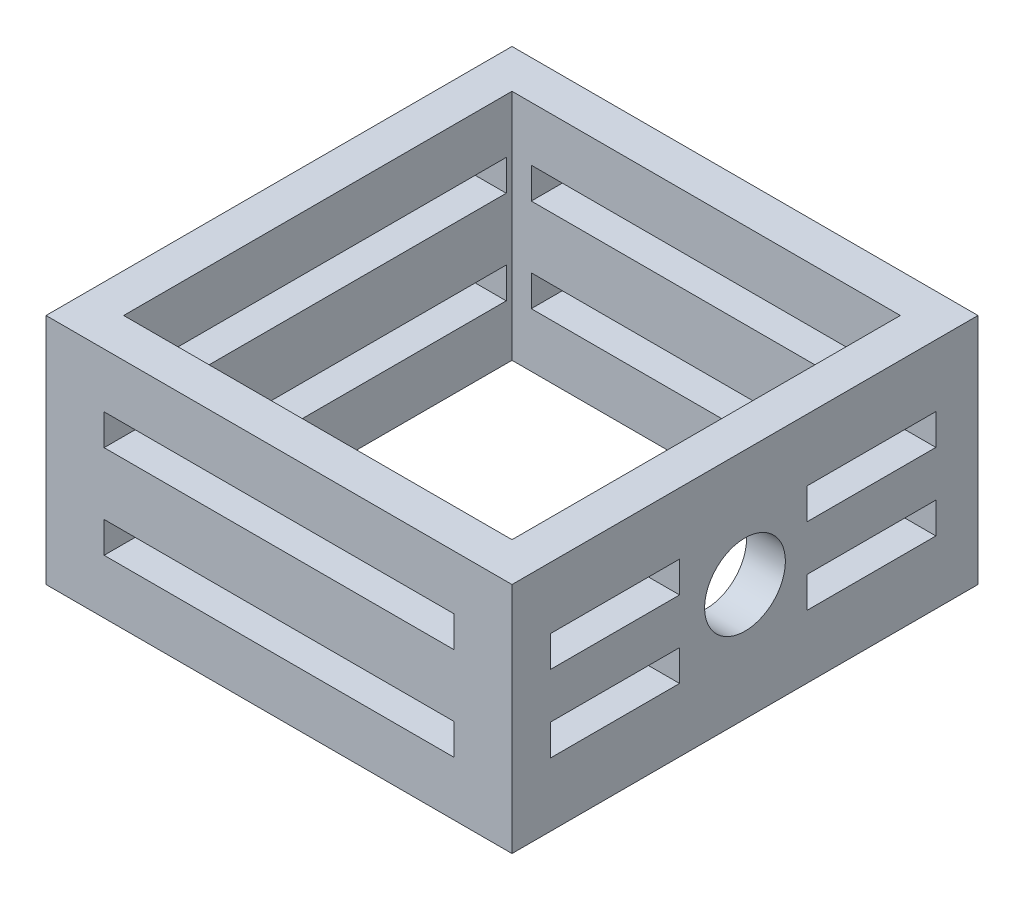
SolidWorks part; units mm, degrees
ref_plane "Front Plane" through (0, 0, 0) normal (0, 0, 1) x (1, 0, 0)
ref_plane "Top Plane" through (0, 0, 0) normal (0, 1, 0) x (1, 0, 0)
ref_plane "Right Plane" through (0, 0, 0) normal (1, 0, 0) x (0, 0, -1)
sketch "Sketch2" plane through (0, 0, 0) normal (0, 1, 0) x (1, 0, 0)
  line L1 (-15, 15) -> (15, 15)
  line L2 (-15, 15) -> (-15, -15)
  line L3 (-15, -15) -> (15, -15)
  line L4 (15, 15) -> (15, -15)
  line L5 (-15, 15) -> (15, -15) construction
  line L6 (-15, -15) -> (15, 15) construction
  point P0 (0, 0)
  dimension "D1" = 30
  dimension "D2" = 30
extrude "Boss-Extrude1" add sketch "Sketch2" along normal blind 10 contours L2 L1 L4 L3
sketch "Sketch3" plane through (0, 10, 0) normal (0, 1, 0) x (1, 0, 0)
  line L1 (-15, 15) -> (15, 15)
  line L2 (-15, 15) -> (-15, -15)
  line L3 (-15, -15) -> (15, -15)
  line L4 (15, 15) -> (15, -15)
  line L5 (-15, 15) -> (15, -15) construction
  line L6 (-15, -15) -> (15, 15) construction
  line L7 (-12.5, 12.5) -> (12.5, 12.5)
  line L8 (-12.5, 12.5) -> (-12.5, -12.5)
  line L9 (-12.5, -12.5) -> (12.5, -12.5)
  line L10 (12.5, 12.5) -> (12.5, -12.5)
  line L11 (-12.5, 12.5) -> (12.5, -12.5) construction
  line L12 (-12.5, -12.5) -> (12.5, 12.5) construction
  point P0 (0, 0)
  point P7 (0, 0)
  dimension "D1" = 25
extrude "Boss-Extrude2" add sketch "Sketch3" along normal blind 15 separate body
sketch "Sketch4" plane through (0, 25, 0) normal (0, 1, 0) x (1, 0, 0)
  line L1 (-15, 15) -> (15, 15)
  line L2 (-15, 15) -> (-15, -15)
  line L3 (-15, -15) -> (15, -15)
  line L4 (15, 15) -> (15, -15)
  line L5 (-15, 15) -> (15, -15) construction
  line L6 (-15, -15) -> (15, 15) construction
  point P0 (0, 0)
extrude "Boss-Extrude3" add sketch "Sketch4" along normal blind 15 separate body
sketch "Sketch5" plane through (0, 40, 0) normal (0, 1, 0) x (1, 0, 0)
  circle A0 centre (0, 0) radius 3.05
extrude "Cut-Extrude1" cut sketch "Sketch5" against normal up to surface (40 mm away) up to face at (0, 0, 0)
delete or keep bodies "Body-Delete/Keep 2" type delete bodies bodies 104 105
sketch "Sketch6" plane through (15, 0, 0) normal (1, 0, 0) x (0, 0, -1)
  line L0 (-15, 17.5) -> (15, 17.5) construction
  line L1 (-15, 25) -> (-15, 10) construction
  line L2 (15, 25) -> (15, 10) construction
  line L3 (3.9909, 19) -> (3.9909, 16) construction
  line L4 (3.5, 21) -> (-3.5, 21)
  line L5 (3.5, 21) -> (3.5, 14)
  line L6 (3.5, 14) -> (-3.5, 14)
  line L7 (-3.5, 21) -> (-3.5, 14)
  line L8 (3.5, 21) -> (-3.5, 14) construction
  line L9 (3.5, 14) -> (-3.5, 21) construction
  line L10 (3.9909, 14.0645) -> (3.9909, 16.0645)
  line L11 (3.9909, 19) -> (12.287, 19)
  line L12 (3.9909, 19) -> (3.9909, 21)
  line L13 (3.9909, 21) -> (12.287, 21)
  line L14 (12.287, 19) -> (12.287, 21)
  line L15 (3.9909, 14.0645) -> (12.287, 14.0645)
  line L16 (12.287, 14.0645) -> (12.287, 16.0645)
  line L17 (3.9909, 16.0645) -> (12.287, 16.0645)
  line L18 (-12.5091, 14.09) -> (-12.5091, 16.09)
  line L19 (-12.5091, 14.09) -> (-4.213, 14.09)
  line L20 (-4.213, 14.09) -> (-4.213, 16.09)
  line L21 (-12.5091, 16.09) -> (-4.213, 16.09)
  line L22 (-12.5091, 19.0255) -> (-12.5091, 21.0255)
  line L23 (-12.5091, 19.0255) -> (-4.213, 19.0255)
  line L24 (-4.213, 19.0255) -> (-4.213, 21.0255)
  line L25 (-12.5091, 21.0255) -> (-4.213, 21.0255)
  circle A0 centre (0, 17.5) radius 2.6
  point P15 (3.9909, 17.5)
  dimension "D1" = 3
  dimension "D2" = 90
  dimension "D3" = 2
  dimension "D4" = 2
extrude "Cut-Extrude2" cut sketch "Sketch6" against normal up to surface (2.5 mm away) contours A0 | L22 L25 L24 L23 | L12 L11 L14 L13 | L10 L17 L16 L15 | L18 L21 L20 L19 up to face at (12.5, 17.5, 0)
sketch "Sketch7" plane through (0, 0, 15) normal (0, 0, 1) x (1, 0, 0)
  line L0 (15, 17.5) -> (-15, 17.5) construction
  line L1 (15, 25) -> (15, 10) construction
  line L2 (-15, 25) -> (-15, 10) construction
  line L3 (0, 14.5) -> (0, 20.5) construction
  line L8 (-11.2591, 15.5) -> (11.2591, 19.5) construction
  line L9 (-11.2591, 19.5) -> (11.1079, 15.5269) construction
  line L15 (-11.2591, 21.5) -> (11.2591, 21.5)
  line L16 (-11.2591, 21.5) -> (-11.2591, 19.5)
  line L17 (-11.2591, 19.5) -> (11.2591, 19.5)
  line L18 (11.2591, 21.5) -> (11.2591, 19.5)
  line L19 (-11.2591, 21.5) -> (11.2591, 19.5) construction
  line L20 (-11.2591, 19.5) -> (11.2591, 21.5) construction
  line L21 (-11.2591, 13.5) -> (11.2591, 13.5)
  line L22 (-11.2591, 13.5) -> (-11.2591, 15.5)
  line L23 (-11.2591, 15.5) -> (11.2591, 15.5)
  line L24 (11.2591, 13.5) -> (11.2591, 15.5)
  line L25 (-11.2591, 13.5) -> (11.2591, 15.5) construction
  line L26 (-11.2591, 15.5) -> (11.2591, 13.5) construction
  point P6 (0, 17.5)
  point P15 (0, 17.5)
  dimension "D1" = 2
  dimension "D2" = 6
extrude "Cut-Extrude3" cut sketch "Sketch7" against normal up to surface (30 mm away) up to face at (0, 17.5, -15)
sketch "Sketch8" plane through (-15, 0, 0) normal (-1, 0, 0) x (0, 0, 1)
  line L0 (-15, 17.5) -> (15, 17.5) construction
  line L1 (-15, 25) -> (-15, 10) construction
  line L2 (15, 25) -> (15, 10) construction
  line L3 (0, 20.5) -> (0, 14.5) construction
  line L5 (12.1303, 21.5) -> (-12.1303, 21.5)
  line L6 (12.1303, 21.5) -> (12.1303, 19.5)
  line L7 (12.1303, 19.5) -> (-12.1303, 19.5)
  line L8 (-12.1303, 21.5) -> (-12.1303, 19.5)
  line L9 (12.1303, 21.5) -> (-12.1303, 19.5) construction
  line L10 (12.1303, 19.5) -> (-12.1303, 21.5) construction
  line L11 (12.1303, 13.5) -> (-12.1303, 13.5)
  line L12 (12.1303, 13.5) -> (12.1303, 15.5)
  line L13 (12.1303, 15.5) -> (-12.1303, 15.5)
  line L14 (-12.1303, 13.5) -> (-12.1303, 15.5)
  line L15 (12.1303, 13.5) -> (-12.1303, 15.5) construction
  line L16 (12.1303, 15.5) -> (-12.1303, 13.5) construction
  point P10 (0, 17.5)
  dimension "D1" = 6
  dimension "D2" = 2
  dimension "D3" = 2
extrude "Cut-Extrude4" cut sketch "Sketch8" against normal up to surface (2.5 mm away) up to face at (-12.5, 17.5, 0)
